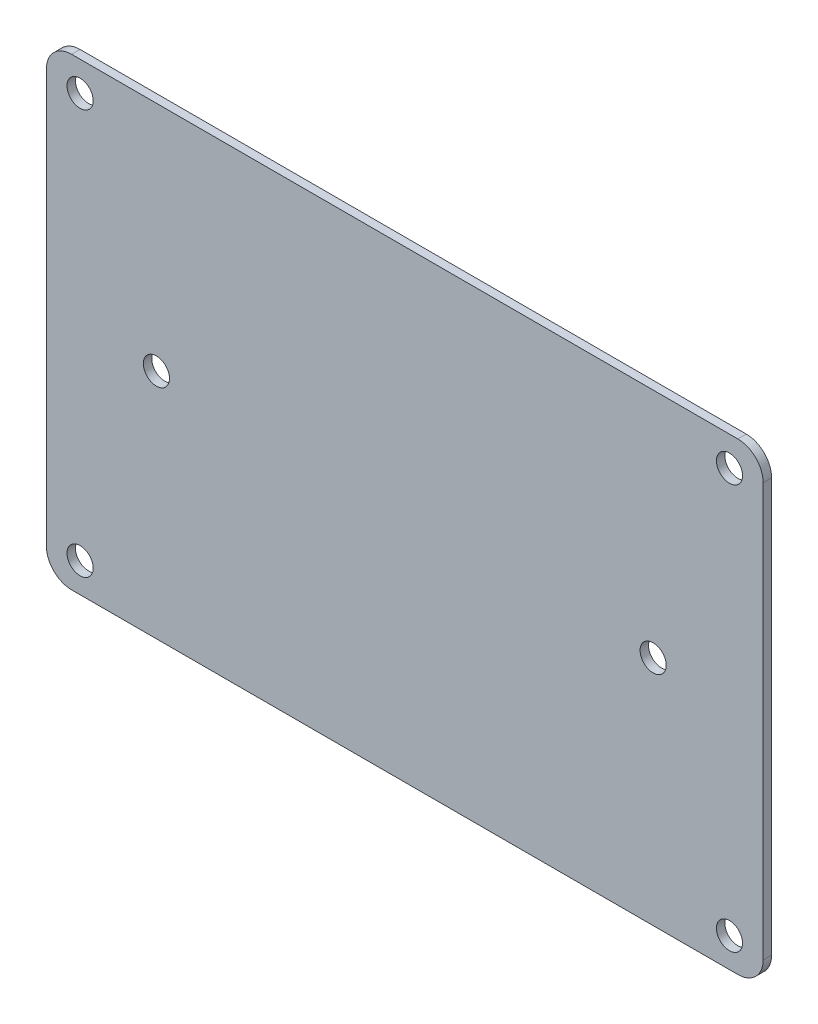
SolidWorks part; units mm, degrees
ref_plane "Front Plane" through (0, 0, 0) normal (0, 0, 1) x (1, 0, 0)
ref_plane "Top Plane" through (0, 0, 0) normal (0, 1, 0) x (1, 0, 0)
ref_plane "Right Plane" through (0, 0, 0) normal (1, 0, 0) x (0, 0, -1)
sketch "Sketch1" plane through (0, 0, 0) normal (0, 0, 1) x (1, 0, 0)
  line L0 (-38.5, 0) -> (0, 0) construction
  line L1 (-39.5, 27.5) -> (39.5, 27.5)
  line L2 (-42.5, 24.5) -> (-42.5, -24.5)
  line L3 (-39.5, -27.5) -> (39.5, -27.5)
  line L4 (42.5, 24.5) -> (42.5, -24.5)
  line L5 (-42.5, 27.5) -> (42.5, -27.5) construction
  line L6 (-42.5, -27.5) -> (42.5, 27.5) construction
  line L7 (-38.5, 0) -> (-38.5, -24) construction
  arc A3 (-39.5, 27.5) -> (-42.5, 24.5) centre (-39.5, 24.5) ccw
  arc A4 (-39.5, -27.5) -> (-42.5, -24.5) centre (-39.5, -24.5) cw
  arc A5 (42.5, -24.5) -> (39.5, -27.5) centre (39.5, -24.5) cw
  arc A6 (39.5, 27.5) -> (42.5, 24.5) centre (39.5, 24.5) cw
  circle A7 centre (-38.5, -24) radius 1.55
  point P0 (0, 0)
  dimension "D3" = 38.5
  dimension "D4" = 3.1
  dimension "D5" = 3
  dimension "D6" = 3
  dimension "D7" = 3
  dimension "D8" = 3
  dimension "D1" = 85
  dimension "D2" = 55
  dimension "D9" = 24
extrude "Boss-Extrude1" add sketch "Sketch1" along normal blind 1
sketch "Sketch3" plane through (0, 0, 0) normal (0, 0, 1) x (1, 0, 0)
  line L0 (0, 0) -> (38.5, 0) construction
  line L1 (38.5, 0) -> (38.5, -24) construction
  circle A1 centre (38.5, -24) radius 1.55
  dimension "D1" = 3.1
  dimension "D2" = 38.5
extrude "Cut-Extrude7" cut sketch "Sketch3" along normal up to next
sketch "Sketch4" plane through (0, 0, 1) normal (0, 0, 1) x (1, 0, 0)
  line L0 (0, 0) -> (-38.5, 0) construction
  line L1 (-38.5, 0) -> (-38.4978, 0.0203)
  line L2 (-38.5, 0) -> (-38.5, 24) construction
  circle A0 centre (-38.5, 24) radius 1.55
  dimension "D3" = 3.1
  dimension "D1" = 38.5
  dimension "D2" = 24
extrude "Cut-Extrude8" cut sketch "Sketch4" against normal through all contours A0 region at (-38.5, 24, 1)
sketch "Sketch7" plane through (0, 0, 1) normal (0, 0, 1) x (1, 0, 0)
  line L0 (0, 0) -> (38.5, 0) construction
  line L1 (38.5, 0) -> (38.5, 24) construction
  circle A0 centre (38.5, 24) radius 1.55
  dimension "D3" = 3.1
  dimension "D1" = 38.5
  dimension "D2" = 24
extrude "Cut-Extrude9" cut sketch "Sketch7" against normal through all contours A0 region at (38.5, 24, 1)
sketch "Sketch8" plane through (0, 0, 0) normal (0, 0, -1) x (-1, 0, 0)
  circle A0 centre (-29.45, 0) radius 1.55
  circle A1 centre (29.45, 0) radius 1.55
  point P4 (20.4949, 0)
  dimension "D1" = 3.1
  dimension "D2" = 3.1
  dimension "D3" = 58.9
extrude "Cut-Extrude10" cut sketch "Sketch8" against normal up to next
